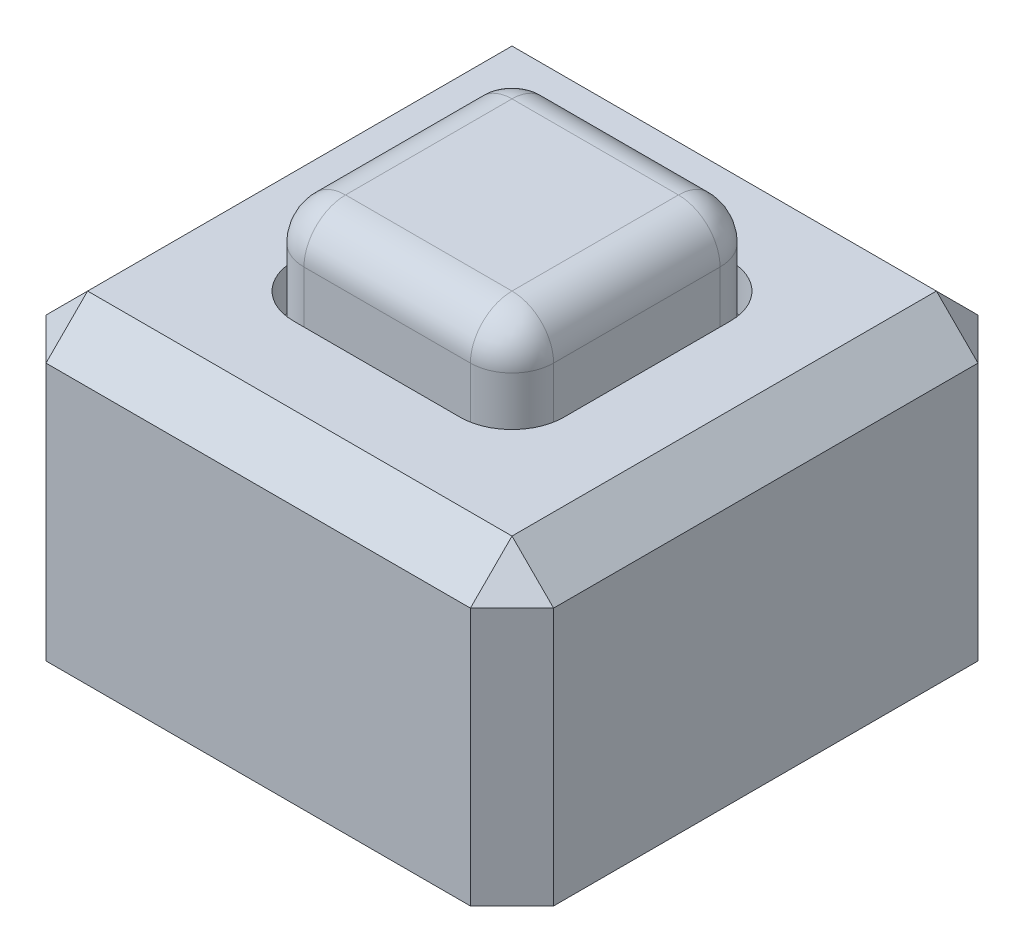
SolidWorks part; units mm, degrees
ref_plane "Front Plane" through (0, 0, 0) normal (0, 0, 1) x (1, 0, 0)
ref_plane "Top Plane" through (0, 0, 0) normal (0, 1, 0) x (1, 0, 0)
ref_plane "Right Plane" through (0, 0, 0) normal (1, 0, 0) x (0, 0, -1)
sketch "Sketch1" plane through (0, 0, 0) normal (0, 1, 0) x (1, 0, 0)
  line L0 (-4, -2) -> (-4, 2)
  line L1 (-2, -3) -> (2, -3)
  line L2 (-3, -2) -> (-3, 2)
  line L3 (-2, 3) -> (2, 3)
  line L4 (3, -2) -> (3, 2)
  line L5 (-3, -3) -> (3, 3) construction
  line L6 (-3, 3) -> (3, -3) construction
  line L7 (-2, 4) -> (2, 4)
  line L8 (4, -2) -> (4, 2)
  line L9 (-2, -4) -> (2, -4)
  arc A0 (-2, -3) -> (-3, -2) centre (-2, -2) cw
  arc A1 (2, -3) -> (3, -2) centre (2, -2) ccw
  arc A2 (2, 3) -> (3, 2) centre (2, 2) cw
  arc A3 (-3, 2) -> (-2, 3) centre (-2, 2) cw
  arc A4 (-4, 2) -> (-2, 4) centre (-2, 2) cw
  arc A5 (2, 4) -> (4, 2) centre (2, 2) cw
  arc A6 (2, -4) -> (4, -2) centre (2, -2) ccw
  arc A7 (-2, -4) -> (-4, -2) centre (-2, -2) cw
  point P0 (0, 0)
  dimension "D1" = 1
  dimension "D2" = 6
  dimension "D3" = 1
extrude "Boss-Extrude1" add sketch "Sketch1" along normal blind 1
extrude "Boss-Extrude2" add sketch "Sketch1<2>" along normal offset from surface (4 mm away) 3 contours A3 L2 A0 L1 A1 L4 A2 L3 region at (0, 0, 0) up to face at (0, 1, 0) offset beyond the face yes
sketch "Sketch1<2>" plane through (0, 0, 0) normal (0, 1, 0) x (1, 0, 0) same geometry as "Sketch1"
fillet "Fillet1" radius 1 8 edges at (2.7071, 4, 2.7071) (3, 4, 0) (2.7071, 4, -2.7071) (0, 4, -3) (-2.7071, 4, -2.7071) (-3, 4, 0) (-2.7071, 4, 2.7071) (0, 4, 3)
sketch "Sketch2" plane through (0, 1, 0) normal (0, 1, 0) x (1, 0, 0)
  line L0 (-2, -3.25) -> (2, -3.25)
  line L1 (3.25, -2) -> (3.25, 2)
  line L2 (2, 3.25) -> (-2, 3.25)
  line L3 (-3.25, 2) -> (-3.25, -2)
  line L4 (-3, 2) -> (-3, -2)
  line L5 (2, 3) -> (-2, 3)
  line L6 (3, -2) -> (3, 2)
  line L7 (-2, -3) -> (2, -3)
  line L8 (-3, 2) -> (-3, -2) construction
  line L9 (2, 3) -> (-2, 3) construction
  line L10 (3, -2) -> (3, 2) construction
  line L11 (-2, -3) -> (2, -3) construction
  line L12 (-6.1, 6.1) -> (-6.1, -6.1)
  line L13 (-3.1, 4.1) -> (3.1, 4.1)
  line L14 (-4.1, 3.1) -> (-4.1, -3.1)
  line L15 (-3.1, -4.1) -> (3.1, -4.1)
  line L16 (4.1, 3.1) -> (4.1, -3.1)
  line L17 (-4.1, 4.1) -> (4.1, -4.1) construction
  line L18 (-4.1, -4.1) -> (4.1, 4.1) construction
  line L19 (-6.1, -6.1) -> (6.1, -6.1)
  line L20 (6.1, 6.1) -> (6.1, -6.1)
  line L21 (-6.1, 6.1) -> (6.1, 6.1)
  line L22 (-4.1, 4.1) -> (4.1, 4.1) construction
  line L23 (4.38, 4.38) -> (-4.38, 4.38) construction
  line L24 (4.38, 4.38) -> (4.38, -4.38) construction
  line L25 (4.38, -4.38) -> (-4.38, -4.38) construction
  line L26 (-4.38, 4.38) -> (-4.38, -4.38) construction
  line L27 (4.38, 4.38) -> (-4.38, -4.38) construction
  line L28 (4.38, -4.38) -> (-4.38, 4.38) construction
  line L29 (-4.1, 4.1) -> (-4.1, -4.1) construction
  line L30 (4.1, 4.1) -> (4.1, -4.1) construction
  line L31 (-4.1, -4.1) -> (4.1, -4.1) construction
  arc A0 (2, -3.25) -> (3.25, -2) centre (2, -2) ccw
  arc A1 (3.25, 2) -> (2, 3.25) centre (2, 2) ccw
  arc A2 (-2, 3.25) -> (-3.25, 2) centre (-2, 2) ccw
  arc A3 (-3.25, -2) -> (-2, -3.25) centre (-2, -2) ccw
  arc A4 (-3, -2) -> (-2, -3) centre (-2, -2) ccw
  arc A5 (-2, 3) -> (-3, 2) centre (-2, 2) ccw
  arc A6 (3, 2) -> (2, 3) centre (2, 2) ccw
  arc A7 (2, -3) -> (3, -2) centre (2, -2) ccw
  arc A8 (-3, -2) -> (-2, -3) centre (-2, -2) ccw construction
  arc A9 (-2, 3) -> (-3, 2) centre (-2, 2) ccw construction
  arc A10 (3, 2) -> (2, 3) centre (2, 2) ccw construction
  arc A11 (2, -3) -> (3, -2) centre (2, -2) ccw construction
  circle A12 centre (-4.38, -4.38) radius 0.2
  circle A13 centre (-4.38, 4.38) radius 0.2
  circle A14 centre (4.38, 4.38) radius 0.2
  circle A15 centre (4.38, -4.38) radius 0.2
  arc A16 (-3.1, 4.1) -> (-4.1, 3.1) centre (-3.1, 3.1) ccw
  arc A17 (3.1, 4.1) -> (4.1, 3.1) centre (3.1, 3.1) cw
  arc A18 (4.1, -3.1) -> (3.1, -4.1) centre (3.1, -3.1) cw
  arc A19 (-4.1, -3.1) -> (-3.1, -4.1) centre (-3.1, -3.1) ccw
  point P24 (0, 0)
  point P34 (0, 0)
  point P43 (4.9221, -4.9221)
  arc M29 (-4, -2) -> (-2, -4) centre (-2, -2) ccw
  line M30 (-2, -4) -> (2, -4)
  arc M31 (2, -4) -> (4, -2) centre (2, -2) ccw
  line M32 (4, -2) -> (4, 2)
  arc M33 (4, 2) -> (2, 4) centre (2, 2) ccw
  line M34 (2, 4) -> (-2, 4)
  arc M35 (-2, 4) -> (-4, 2) centre (-2, 2) ccw
  line M36 (-4, 2) -> (-4, -2)
  dimension "D5" = 0.4
  dimension "D7" = 1
  dimension "D4" = 8.2
  dimension "D6" = 8.76
  dimension "D1" = 0
  dimension "D2" = 0.25
  dimension "D3" = 2
extrude "Boss-Extrude3" add sketch "Sketch2" against normal blind 6.2 separate body contours L21 L12 L19 L20 A19 L14 A16 L13 A17 L16 A18 L15 A15 A14 A13 A12 region at (0, 1, -5.9275)
extrude "Boss-Extrude4" add sketch "Sketch2<3>" along normal blind 1 contours A3 L3 A2 L2 A1 L1 A0 L0 M36 M29 M30 M31 M32 M33 M34 M35 | L21 L12 L19 L20 A19 L14 A16 L13 A17 L16 A18 L15 A15 A14 A13 A12 | L14 A19 L15 A18 L16 A17 L13 A16 M29 M36 M35 M34 M33 M32 M31 M30 | A15 | A12 | A13 | A14 region at (0, 1, -5.9275) region at (0, 1, -4.0884) region at (-4.38, 1, 4.38) region at (-4.38, 1, -4.38) region at (4.38, 1, -4.38) region at (4.38, 1, 4.38) region at (-3.8869, 1, 0)
sketch "Sketch2<3>" plane through (0, 1, 0) normal (0, 1, 0) x (1, 0, 0) same geometry as "Sketch2"
chamfer "Chamfer1" distance 1 angle 45 8 edges at (-6.1, -1.6, -6.1) (0, 2, -6.1) (6.1, -1.6, -6.1) (6.1, 2, 0) (6.1, -1.6, 6.1) (-6.1, 2, 0) (-6.1, -1.6, 6.1) (0, 2, 6.1)
equation "\"D1@Boss-Extrude3\"=5.2+1"
